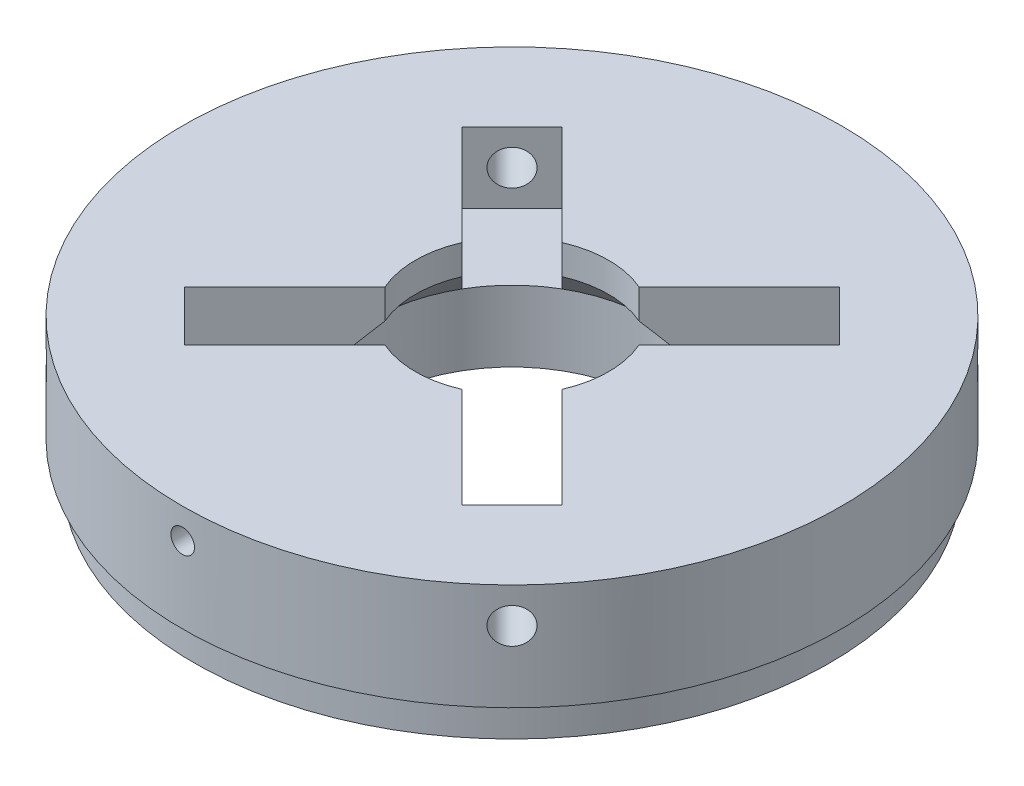
SolidWorks part; units mm, degrees
ref_plane "Front" through (0, 0, 0) normal (0, 0, 1) x (1, 0, 0)
ref_plane "Top" through (0, 0, 0) normal (0, 1, 0) x (1, 0, 0)
ref_plane "Right" through (0, 0, 0) normal (1, 0, 0) x (0, 0, -1)
sketch "Sketch1" plane through (0, 0, 0) normal (0, 1, 0) x (1, 0, 0)
  line L0 (11.7436, 15.9863) -> (3.2583, 7.501)
  line L1 (-9.6223, -9.6223) -> (9.6223, -9.6223) construction
  line L2 (-9.6223, -9.6223) -> (-9.6223, 9.6223) construction
  line L3 (-9.6223, 9.6223) -> (9.6223, 9.6223) construction
  line L4 (9.6223, -9.6223) -> (9.6223, 9.6223) construction
  line L5 (-9.6223, -9.6223) -> (9.6223, 9.6223) construction
  line L6 (-9.6223, 9.6223) -> (9.6223, -9.6223) construction
  line L7 (11.7436, 15.9863) -> (15.9863, 11.7436)
  line L9 (15.9863, 11.7436) -> (7.501, 3.2583)
  line L10 (11.7436, 15.9863) -> (7.501, 3.2583) construction
  line L11 (3.2583, 7.501) -> (15.9863, 11.7436) construction
  line L12 (-15.9863, 11.7436) -> (-7.501, 3.2583)
  line L13 (-15.9863, 11.7436) -> (-11.7436, 15.9863)
  line L15 (-11.7436, 15.9863) -> (-3.2583, 7.501)
  line L16 (-15.9863, 11.7436) -> (-3.2583, 7.501) construction
  line L17 (-7.501, 3.2583) -> (-11.7436, 15.9863) construction
  line L18 (-15.9863, -11.7436) -> (-7.501, -3.2583)
  line L19 (-15.9863, -11.7436) -> (-11.7436, -15.9863)
  line L21 (-11.7436, -15.9863) -> (-3.2583, -7.501)
  line L22 (-15.9863, -11.7436) -> (-3.2583, -7.501) construction
  line L23 (-7.501, -3.2583) -> (-11.7436, -15.9863) construction
  line L24 (11.7436, -15.9863) -> (3.2583, -7.501)
  line L25 (11.7436, -15.9863) -> (15.9863, -11.7436)
  line L27 (15.9863, -11.7436) -> (7.501, -3.2583)
  line L28 (11.7436, -15.9863) -> (7.501, -3.2583) construction
  line L29 (3.2583, -7.501) -> (15.9863, -11.7436) construction
  line L30 (-15.9863, -11.7436) -> (-7.501, -3.2583) construction
  line L31 (-11.7436, -15.9863) -> (-15.9863, -11.7436) construction
  circle A0 centre (0, 0) radius 27.8896
  circle A1 centre (0, 0) radius 3.5
  circle A2 centre (0, 0) radius 3.5 construction
  circle A3 centre (0, 0) radius 27.8896 construction
  arc A4 (-3.2583, -7.501) -> (3.2583, -7.501) centre (0, 0) ccw
  arc A5 (7.501, -3.2583) -> (7.501, 3.2583) centre (0, 0) ccw
  arc A6 (3.2583, 7.501) -> (-3.2583, 7.501) centre (0, 0) ccw
  arc A7 (-7.501, 3.2583) -> (-7.501, -3.2583) centre (0, 0) ccw
extrude "Boss-Extrude1" add sketch "Sketch1" along normal blind 6 contours A0 A7 L12 L13 L15 A6 L0 L7 L9 A5 L27 L25 L24 A4 L21 L19 L18 region at (-27.1008, 0, 0)
sketch "Sketch2" plane through (13.8649, 0, -13.8649) normal (-0.7071, 0, 0.7071) x (0.7071, 0, 0.7071)
  line L0 (3, 6) -> (-3, 0) construction
  line L1 (-3, 0) -> (3, 0) construction
  line L2 (3, 0) -> (-3, 6) construction
  circle A0 centre (0, 3) radius 1.5
  dimension "D1" = 3
extrude "Cut-Extrude1" cut sketch "Sketch2" against normal up to next
pattern_circular "CirPattern1" count 4 over 360 about axis through (0, 6, 0) along (0, -1, 0) of "Cut-Extrude1"
chamfer "Chamfer1" distance 3.5 angle 45 4 edges at (0, 0, 8.1781) (8.1781, 0, 0) (0, 0, -8.1781) (-8.1781, 0, 0)
sketch "Sketch3" plane through (0, 0, 0) normal (0, -1, 0) x (1, 0, 0)
  circle A0 centre (0, 0) radius 27.8896
  circle A1 centre (0, 0) radius 11.6781
extrude "Boss-Extrude2" add sketch "Sketch3" along normal blind 6
ref_plane "Plane1" through (0, 0, 27.8896) normal (0, 0, 1) x (1, 0, 0)
sketch "Sketch4" plane through (0, 0, 27.8896) normal (0, 0, 1) x (1, 0, 0)
  circle A0 centre (0, 3.4617) radius 1
  dimension "D1" = 2
extrude "Cut-Extrude2" cut sketch "Sketch4" against normal up to next
sketch "Sketch5" plane through (0, -6, 0) normal (0, -1, 0) x (1, 0, 0)
  circle A0 centre (0, 0) radius 19.0318
  circle A1 centre (21.9804, 1.5041) radius 3 construction
  circle A2 centre (21.5711, -4.482) radius 3 construction
  circle A3 centre (11.4479, -18.8241) radius 3 construction
  circle A4 centre (5.9447, -21.2147) radius 3 construction
  circle A5 centre (0.0006, -22.0318) radius 3 construction
  circle A6 centre (-5.9436, -21.215) radius 3 construction
  circle A7 centre (-11.4469, -18.8247) radius 3 construction
  circle A8 centre (-16.1013, -15.0383) radius 3 construction
  circle A9 centre (-16.1013, -15.0383) radius 3 construction
  circle A10 centre (-19.5615, -10.1366) radius 3 construction
  circle A11 centre (-21.5709, -4.4831) radius 3 construction
  circle A12 centre (-21.9805, 1.5029) radius 3 construction
  circle A13 centre (-20.7599, 7.3775) radius 3 construction
  circle A14 centre (-17.9997, 12.7049) radius 3 construction
  circle A15 centre (-13.9045, 17.09) radius 3 construction
  circle A16 centre (-8.778, 20.2076) radius 3 construction
  circle A17 centre (-3.0006, 21.8265) radius 3 construction
  circle A18 centre (2.9994, 21.8267) radius 3 construction
  circle A19 centre (8.777, 20.2081) radius 3 construction
  circle A20 centre (13.9036, 17.0907) radius 3 construction
  circle A21 centre (17.999, 12.7058) radius 3 construction
  circle A22 centre (20.7595, 7.3785) radius 3 construction
  circle A23 centre (0, 0) radius 25.0318
  circle A24 centre (19.562, -10.1356) radius 3 construction
  circle A25 centre (16.102, -15.0375) radius 3 construction
  circle A26 centre (0, 0) radius 27.8896
  circle A27 centre (0, 0) radius 26.8896
  circle A29 centre (0, 0) radius 27.8896 construction
  circle M1 centre (0, 0) radius 27.8896
  dimension "D1" = 6
  dimension "D2" = 1
extrude "Cut-Extrude3" cut sketch "Sketch5" against normal blind 3 contours A23 A0 | A27 M1 region at (-24.3238, -6, 0) region at (-27.1008, -6, 0)
fillet "Fillet1" radius 3 2 edges at (0, -3, -25.0318) (0, -3, -19.0318)
